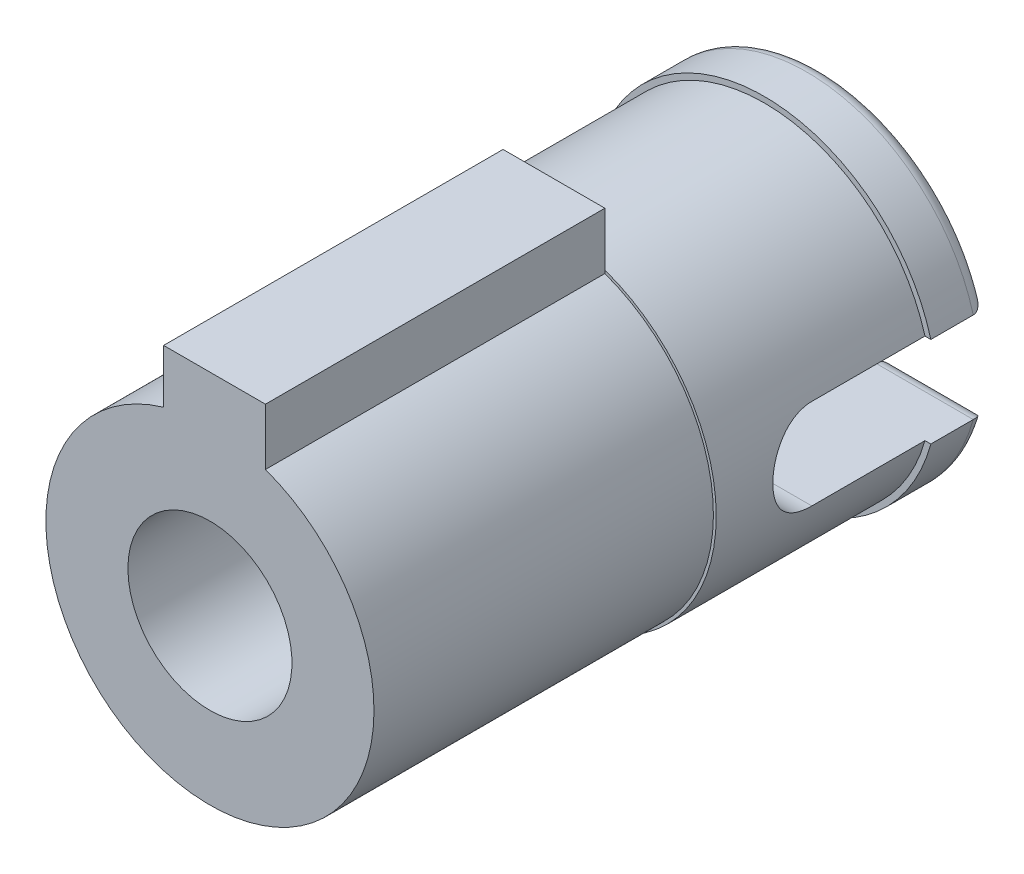
SolidWorks part; units mm, degrees
note: The reader was unsure of these and kept them because the rebuilt part matched: shared geometry of "Sketch1<4>".
ref_plane "Front Plane" through (0, 0, 0) normal (1, 0, 0) x (0, 1, 0)
ref_plane "Top Plane" through (0, 0, 0) normal (0, 0, 1) x (0, 1, 0)
ref_plane "Right Plane" through (0, 0, 0) normal (0, 1, 0) x (-1, 0, 0)
sketch "Sketch1" plane through (0, 0, 0) normal (0, 0, 1) x (0, 1, 0)
  circle A0 centre (0, 0) radius 2.95
  circle A1 centre (0, 0) radius 1.45
  dimension "D1" = 5.9
  dimension "D2" = 1.5
extrude "Boss-Extrude1" add sketch "Sketch1" along normal blind 4.8 contours A0
sketch "Sketch10" plane through (0, 0, 0) normal (0, 0, 1) x (0, 1, 0)
  circle A0 centre (0, 0) radius 3.05
  circle A1 centre (0, 0) radius 2.95 construction
  dimension "D1" = 0.1
extrude "Boss-Extrude2" add sketch "Sketch10" along normal blind 1 contours A0
sketch "Sketch3" plane through (0, 0, 0) normal (1, 0, 0) x (0, 1, 0)
  line L0 (0, -0.3447) -> (0, 3) construction
  line L1 (-0.8, -0.3447) -> (-0.8, 3)
  line L2 (0.8, -0.3447) -> (0.8, 3)
  line L3 (1.45, 0) -> (-1.45, 0) construction
  arc A0 (-0.8, -0.3447) -> (0.8, -0.3447) centre (0, -0.3447) ccw
  arc A1 (0.8, 3) -> (-0.8, 3) centre (0, 3) ccw
  point P3 (0, 1.3277)
  dimension "D2" = 0.8
  dimension "D1" = 3
extrude "Cut-Extrude2" cut sketch "Sketch3" against normal through all and the other way through all
extrude "Cut-Extrude1" cut sketch "Sketch1<4>" along normal blind 9 contours A1
sketch "Sketch1<4>" plane through (0, 0, 0) normal (0, 0, 1) x (0, 1, 0) same geometry as "Sketch1"
sketch "Sketch11" plane through (0, 0, 4.8) normal (0, 0, 1) x (1, 0, 0)
  line L0 (-0.8185, 3.7289) -> (0.9815, 3.7289)
  line L1 (-0.8185, 3.7289) -> (-0.8185, 2.7821)
  line L2 (0.9815, 3.7289) -> (0.9815, 2.7289)
  arc A0 (-0.8185, 2.7821) -> (0.9815, 2.7289) centre (0, 0) ccw
  dimension "D3" = 2.9
  dimension "D1" = 1
  dimension "D2" = 1.8
extrude "Boss-Extrude3" add sketch "Sketch11" along normal blind 6
sketch "Sketch12" plane through (0, 0, 4.8) normal (0, 0, -1) x (1, 0, 0)
  circle A0 centre (0, 0) radius 1.45
  dimension "D1" = 2.9
extrude "Cut-Extrude3" cut sketch "Sketch12" against normal through all
fillet "Fillet2" radius 0.25 8 edges at (0, 3.05, 0) (0, -3.05, 0) (2.0763, 0.8, 0) (-2.0763, -0.8, 0) (-2.0763, 0.8, 0) (2.0763, -0.8, 0) (0, 1.45, 0) (0, -1.45, 0)
